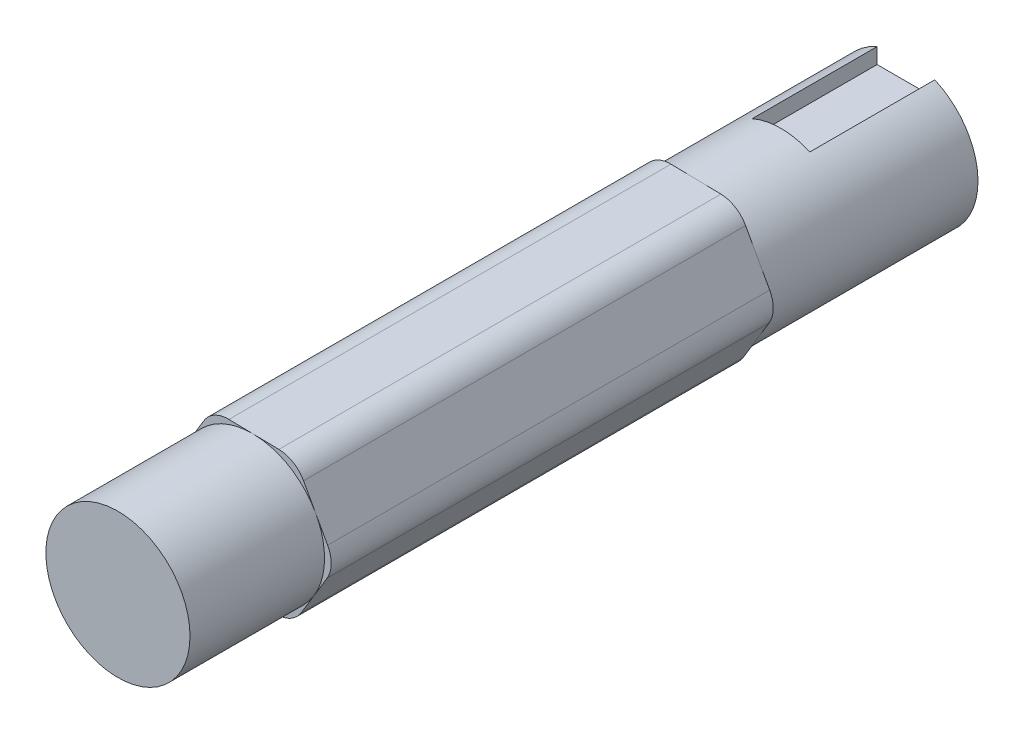
SolidWorks part; units mm, degrees
ref_plane "Front Plane" through (0, 0, 0) normal (0, 0, 1) x (1, 0, 0)
ref_plane "Top Plane" through (0, 0, 0) normal (0, 1, 0) x (1, 0, 0)
ref_plane "Right Plane" through (0, 0, 0) normal (1, 0, 0) x (0, 0, -1)
sketch "Sketch1" plane through (0, 0, 0) normal (0, 0, 1) x (1, 0, 0)
  circle A0 centre (0, 0) radius 7.5
  dimension "D1" = 15
extrude "Boss-Extrude1" add sketch "Sketch1" along normal blind 37 and the other way blind 45
sketch "Sketch3" plane through (0, 0, 0) normal (0, 1, 0) x (1, 0, 0)
  line L0 (-27.349, 0) -> (27.9883, 0) construction
  line L1 (-27.349, 31) -> (27.9883, 31) construction
  line L2 (-27.349, 32) -> (27.9883, 32) construction
  line L3 (-27.349, 42) -> (27.9883, 42) construction
  line L4 (27.9883, 45) -> (-27.349, 45) construction
  line L5 (-27.349, -31) -> (27.9883, -31) construction
  line L6 (-27.349, -37) -> (27.9883, -37) construction
  dimension "D1" = 31
  dimension "D2" = 1
  dimension "D3" = 10
  dimension "D4" = 3
  dimension "D5" = 31
  dimension "D6" = 6
sketch "Sketch4" plane through (0, 0, -45) normal (0, 0, -1) x (-1, 0, 0)
  line L0 (-18.2857, 7.5) -> (18.9059, 7.5) construction
  line L1 (-3, 9.75) -> (3, 9.75)
  line L2 (-3, 9.75) -> (-3, 5.25)
  line L3 (-3, 5.25) -> (3, 5.25)
  line L4 (3, 9.75) -> (3, 5.25)
  line L5 (0, 15.7597) -> (0, -12.3933) construction
  circle A0 centre (0, 0) radius 7.5 construction
  dimension "D1" = 6
  dimension "D2" = 4.5
extrude "Cut-Extrude1" cut sketch "Sketch4" against normal blind 13
ref_plane "Plane1" through (0, 0, 23) normal (0, 0, 1) x (1, 0, 0)
ref_plane "Plane2" through (0, 0, -23) normal (0, 0, 1) x (1, 0, 0)
sketch "Sketch5" plane through (0, 0, -23) normal (0, 0, 1) x (1, 0, 0)
  line L1 (4.4795, 7.4118) -> (-4.179, 7.5852)
  line L2 (-4.179, 7.5852) -> (-8.6585, 0.1735)
  line L3 (-8.6585, 0.1735) -> (-4.4795, -7.4118)
  line L4 (-4.4795, -7.4118) -> (4.179, -7.5852)
  line L5 (4.179, -7.5852) -> (8.6585, -0.1735)
  line L6 (8.6585, -0.1735) -> (4.4795, 7.4118)
  circle A0 centre (0, 0) radius 7.5 construction
  dimension "D1" = 15
extrude "Boss-Extrude2" add sketch "Sketch5" along normal up to surface (46 mm away) up to plane "Plane1"
fillet "Fillet1" radius 3 6 edges at (-4.179, 7.5852, 0) (-8.6585, 0.1735, 0) (-4.4795, -7.4118, 0) (4.179, -7.5852, 0) (8.6585, -0.1735, 0) (4.4795, 7.4118, 0)
